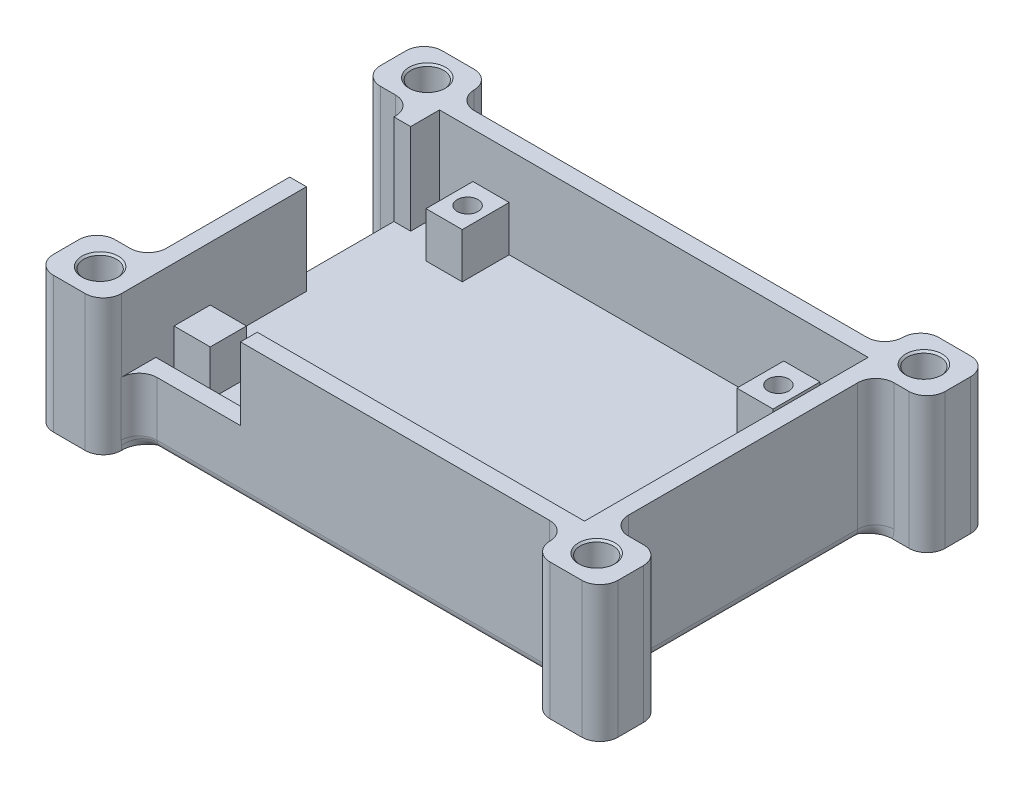
SolidWorks part; units mm, degrees
ref_plane "Płaszczyzna przednia" through (0, 0, 0) normal (0, 0, 1) x (1, 0, 0)
ref_plane "Płaszczyzna górna" through (0, 0, 0) normal (0, 1, 0) x (1, 0, 0)
ref_plane "Płaszczyzna prawa" through (0, 0, 0) normal (1, 0, 0) x (0, 0, -1)
sketch "Szkic1" plane through (0, 0, 0) normal (0, 1, 0) x (1, 0, 0)
  line L1 (-23.65, -15.65) -> (23.65, -15.65)
  line L2 (-23.65, -15.65) -> (-23.65, 15.65)
  line L3 (-23.65, 15.65) -> (23.65, 15.65)
  line L4 (23.65, -15.65) -> (23.65, 15.65)
  line L5 (-23.65, -15.65) -> (23.65, 15.65) construction
  line L6 (-23.65, 15.65) -> (23.65, -15.65) construction
  point P0 (0, 0)
  dimension "D1" = 47.3
  dimension "D2" = 31.3
extrude "Dodanie-wyciągnięcie1" add sketch "Szkic1" along normal blind 10
shell "Skorupa1" thickness 5 removed face at (0, 10, 0) outward yes
sketch "Szkic4" plane through (0, 0, 0) normal (0, 1, 0) x (1, 0, 0)
  line L0 (23.65, -15.65) -> (23.65, 15.65) construction
  line L1 (23.65, 15.65) -> (-23.65, 15.65) construction
  line L2 (-23.65, 15.65) -> (-23.65, -15.65) construction
  line L3 (23.65, 15.65) -> (-23.65, 15.65) construction
  line L4 (-23.65, -15.65) -> (23.65, -15.65) construction
  line L6 (23.65, -15.65) -> (23.65, 15.65) construction
  line L7 (-19.96, 10.47) -> (-15.96, 10.47)
  line L8 (-19.96, 10.47) -> (-19.96, 15.65)
  line L9 (-19.96, 15.65) -> (-15.96, 15.65)
  line L10 (-15.96, 10.47) -> (-15.96, 15.65)
  line L11 (-19.96, 10.47) -> (-15.96, 15.65) construction
  line L12 (-19.96, 15.65) -> (-15.96, 10.47) construction
  line L13 (14.34, 10.47) -> (18.34, 10.47)
  line L14 (14.34, 10.47) -> (14.34, 15.65)
  line L15 (14.34, 15.65) -> (18.34, 15.65)
  line L16 (18.34, 10.47) -> (18.34, 15.65)
  line L17 (14.34, 10.47) -> (18.34, 15.65) construction
  line L18 (14.34, 15.65) -> (18.34, 10.47) construction
  circle A0 centre (-17.96, 13.06) radius 1.15
  circle A1 centre (16.34, 13.06) radius 1.15
  circle A2 centre (5.63, -12.865) radius 1.15
  point P16 (-11.417, 13.06)
  dimension "D1" = 2.3
  dimension "D2" = 7.31
  dimension "D3" = 2.59
  dimension "D4" = 5.69
  dimension "D5" = 2.59
  dimension "D6" = 2.785
  dimension "D7" = 18.02
  dimension "D8" = 4
  dimension "D9" = 4
extrude "Dodanie-wyciągnięcie2" add sketch "Szkic4" along normal blind 5
sketch "Szkic5" plane through (0, 0, 20.65) normal (0, 0, 1) x (1, 0, 0)
  line L0 (-28.65, 10) -> (-28.65, -5) construction
  line L1 (-23.56, 10) -> (-12.46, 10)
  line L2 (-23.56, 10) -> (-23.56, 2)
  line L3 (-23.56, 2) -> (-12.46, 2)
  line L4 (-12.46, 10) -> (-12.46, 2)
  line L7 (-28.65, 10) -> (28.65, 10) construction
  point P0 (-19.96, 7.5)
  dimension "D1" = 7.5
  dimension "D2" = 8.69
  dimension "D3" = 8
  dimension "D4" = 0
extrude "Wytnij-wyciągnięcie2" cut sketch "Szkic5" against normal blind 7
sketch "Szkic7" plane through (0, -5, 0) normal (0, -1, 0) x (1, 0, 0)
  line L0 (-28.65, 20.65) -> (28.65, 20.65) construction
  line L1 (-10.65, 0.65) -> (-4.65, 0.65)
  line L2 (-10.65, 0.65) -> (-10.65, 6.65)
  line L3 (-10.65, 6.65) -> (-4.65, 6.65)
  line L4 (-4.65, 0.65) -> (-4.65, 6.65)
  line L5 (-10.65, 0.65) -> (-4.65, 6.65) construction
  line L6 (-10.65, 6.65) -> (-4.65, 0.65) construction
  line L7 (-28.65, -20.65) -> (-28.65, 20.65) construction
  point P0 (-7.65, 3.65)
  dimension "D1" = 14
  dimension "D2" = 18
  dimension "D3" = 6
  dimension "D4" = 6
extrude "Wytnij-wyciągnięcie4" [suppressed] cut sketch "Szkic7" against normal blind 7
sketch "Szkic8" plane through (0, -5, 0) normal (0, -1, 0) x (1, 0, 0)
  line L1 (-25.5, -17.5) -> (25.5, -17.5)
  line L2 (-25.5, -17.5) -> (-25.5, 17.5)
  line L3 (-25.5, 17.5) -> (25.5, 17.5)
  line L4 (25.5, -17.5) -> (25.5, 17.5)
  line L5 (-25.5, -17.5) -> (25.5, 17.5) construction
  line L6 (-25.5, 17.5) -> (25.5, -17.5) construction
  line L7 (-28.65, -20.65) -> (28.65, -20.65)
  line L8 (-28.65, -20.65) -> (-28.65, 20.65)
  line L9 (-28.65, 20.65) -> (28.65, 20.65)
  line L10 (28.65, -20.65) -> (28.65, 20.65)
  line L11 (-28.65, -20.65) -> (28.65, 20.65) construction
  line L12 (-28.65, 20.65) -> (28.65, -20.65) construction
  point P0 (0, 0)
  point P6 (0, 0)
  dimension "D1" = 51
  dimension "D2" = 35
extrude "Wytnij-wyciągnięcie5" cut sketch "Szkic8" against normal blind 17
fillet "Zaokrąglenie1" [suppressed] radius 2
sketch "Szkic9" plane through (0, 0, 0) normal (0, 1, 0) x (1, 0, 0)
  line L0 (23.65, -15.65) -> (23.65, 15.65) construction
  line L1 (18.65, -10.65) -> (22.65, -10.65)
  line L2 (18.65, -10.65) -> (18.65, -14.65)
  line L3 (18.65, -14.65) -> (22.65, -14.65)
  line L4 (22.65, -10.65) -> (22.65, -14.65)
  line L5 (18.65, -10.65) -> (22.65, -14.65) construction
  line L6 (18.65, -14.65) -> (22.65, -10.65) construction
  line L7 (-12.46, -15.65) -> (23.65, -15.65) construction
  line L8 (0, 0) -> (0, -15.65) construction
  line L9 (-23.65, -15.65) -> (23.65, -15.65) construction
  line L10 (-22.65, -10.65) -> (-22.65, -14.65)
  line L11 (-18.65, -10.65) -> (-18.65, -14.65)
  line L12 (-18.65, -10.65) -> (-22.65, -10.65)
  line L13 (-18.65, -14.65) -> (-22.65, -14.65)
  point P0 (20.65, -12.65)
  dimension "D1" = 4
  dimension "D2" = 4
  dimension "D3" = 5
  dimension "D4" = 5
extrude "Dodanie-wyciągnięcie3" add sketch "Szkic9" along normal blind 5 contours L13 L11 L12 L10 | L1 L4 L3 L2 region at (-20.65, 0, 12.65)
sketch "Szkic6" plane through (-25.5, 0, 0) normal (-1, 0, 0) x (0, 0, 1)
  line L13 (-0.9672, 0) -> (-12.4672, 0)
  line L14 (-0.9672, 0) -> (-0.9672, 10)
  line L15 (-0.9672, 10) -> (-12.4672, 10)
  line L16 (-12.4672, 0) -> (-12.4672, 10)
  line L17 (-0.9672, 0) -> (-12.4672, 10) construction
  line L18 (-0.9672, 10) -> (-12.4672, 0) construction
  point P0 (-8, 3)
  point P5 (-8, 3)
  point P10 (-6.7172, 5)
  dimension "D1" = 11.5
extrude "Wytnij-wyciągnięcie3" cut sketch "Szkic6" against normal blind 2
extrude "Wytnij-wyciągnięcie6" cut sketch "Szkic4<2>" against normal blind 10 contours A1 | A2 | A0 region at (16.34, 0, -13.06) region at (5.63, 0, 12.865)
sketch "Szkic4<2>" plane through (0, 0, 0) normal (0, 1, 0) x (1, 0, 0) same geometry as "Szkic4"
sketch "Szkic10" plane through (0, -5, 0) normal (0, -1, 0) x (1, 0, 0)
  line L0 (5.63, 17.5) -> (5.63, 9.0163) construction
  line L2 (7.993, 12.7243) -> (7.9225, 12.865)
  line L3 (5.7518, 14.9114) -> (5.63, 14.9186)
  line L6 (5.5082, 10.8186) -> (5.63, 10.8114)
  line L19 (25.5, 17.5) -> (-25.5, 17.5) construction
  line L20 (5.63, 12.865) -> (9.7087, 12.865) construction
  line L21 (16.34, -13.06) -> (16.34, -10.331) construction
  line L22 (6.6896, 10.7483) -> (7.3413, 11.7363) [skipped]
  line L23 (3.267, 13.0057) -> (3.7969, 11.9473) [skipped]
  line L24 (4.5704, 14.9817) -> (3.9187, 13.9937) [skipped]
  line L25 (7.9971, 12.865) -> (6.8136, 14.915)
  line L26 (6.8136, 14.915) -> (4.4464, 14.915)
  line L27 (4.4464, 14.915) -> (3.2629, 12.865)
  line L28 (3.2629, 12.865) -> (4.4464, 10.815)
  line L29 (4.4464, 10.815) -> (6.8136, 10.815)
  line L30 (6.8136, 10.815) -> (7.9971, 12.865)
  line L31 (16.34, -13.06) -> (19.1063, -13.06) construction
  line L32 (-17.96, -13.06) -> (-17.96, -9.9123) construction
  line L33 (18.7071, -13.06) -> (17.5236, -11.01)
  line L34 (17.5236, -11.01) -> (15.1564, -11.01)
  line L35 (15.1564, -11.01) -> (13.9729, -13.06)
  line L36 (13.9729, -13.06) -> (15.1564, -15.11)
  line L37 (15.1564, -15.11) -> (17.5236, -15.11)
  line L38 (17.5236, -15.11) -> (18.7071, -13.06)
  line L39 (-17.96, -13.06) -> (-14.4053, -13.06) construction
  line L41 (-15.5929, -13.06) -> (-16.7764, -11.01)
  line L42 (-16.7764, -11.01) -> (-19.1436, -11.01)
  line L43 (-19.1436, -11.01) -> (-20.3271, -13.06)
  line L44 (-20.3271, -13.06) -> (-19.1436, -15.11)
  line L45 (-19.1436, -15.11) -> (-16.7764, -15.11)
  line L46 (-16.7764, -15.11) -> (-15.5929, -13.06)
  circle A2 centre (5.63, 12.865) radius 2.3671
  circle A3 centre (16.34, -13.06) radius 2.05 construction
  circle A4 centre (16.34, -13.06) radius 2.3671
  circle A5 centre (-17.96, -13.06) radius 2.05 construction
  circle A6 centre (-17.96, -13.06) radius 2.3671
  circle M11 centre (16.34, -13.06) radius 1.15
  circle M13 centre (-17.96, -13.06) radius 1.15
  dimension "D3" = 4.1
extrude "Wytnij-wyciągnięcie7" cut sketch "Szkic10" against normal blind 4 contours M13 | M11 | L25 L26 L27 L28 L29 L30 region at (18.0611, -5, -14.0537) region at (-16.2389, -5, -14.0537)
fillet "Zaokrąglenie4" radius 1 4 edges at (0, -5, 17.5) (-25.5, -5, 0) (25.5, -5, 0) (0, -5, -17.5)
fillet "Zaokrąglenie6" [suppressed] radius 1.5
sketch "Szkic11" plane through (0, 10, 0) normal (0, 1, 0) x (1, 0, 0)
  line L1 (-23.65, -21.4503) -> (-31.15, -21.4503)
  line L2 (-23.65, -21.4503) -> (-23.65, -14.6503)
  line L3 (-23.65, -14.6503) -> (-31.15, -14.6503)
  line L4 (-31.15, -21.4503) -> (-31.15, -14.6503)
  line L5 (-23.65, -21.4503) -> (-31.15, -14.6503) construction
  line L6 (-23.65, -14.6503) -> (-31.15, -21.4503) construction
  line L7 (-28.65, 0) -> (28.65, 0) construction
  line L10 (0, 20.65) -> (0, -20.65) construction
  line L13 (-23.65, 14.6503) -> (-31.15, 14.6503)
  line L14 (-31.15, 21.4503) -> (-31.15, 14.6503)
  line L15 (-23.65, 21.4503) -> (-31.15, 21.4503)
  line L16 (-23.65, 21.4503) -> (-23.65, 14.6503)
  line L17 (23.65, -14.6503) -> (31.15, -14.6503)
  line L18 (31.15, -21.4503) -> (31.15, -14.6503)
  line L19 (23.65, -21.4503) -> (31.15, -21.4503)
  line L20 (23.65, -21.4503) -> (23.65, -14.6503)
  line L21 (23.65, 21.4503) -> (23.65, 14.6503)
  line L22 (23.65, 21.4503) -> (31.15, 21.4503)
  line L23 (31.15, 21.4503) -> (31.15, 14.6503)
  line L24 (23.65, 14.6503) -> (31.15, 14.6503)
  line L25 (-23.65, 0.9672) -> (-23.65, -15.65) construction
  circle A0 centre (-27.4, -18.0503) radius 1.81
  circle A1 centre (-27.4, 18.0503) radius 1.81
  circle A2 centre (27.4, 18.0503) radius 1.81
  circle A3 centre (27.4, -18.0503) radius 1.81
  dimension "D2" = 3.62
  dimension "D1" = 7.5
  dimension "D3" = 6.8
sketch "Szkic12" plane through (0, 10, 0) normal (0, 1, 0) x (1, 0, 0)
  line L0 (-23.65, -21.4503) -> (-31.15, -14.6503) construction
  line L1 (-28.65, 0) -> (28.65, 0) construction
  line L2 (0, 20.65) -> (0, -20.65) construction
  circle A0 centre (-27.4, -18.0503) radius 1.225
  circle A1 centre (-27.4, 18.0503) radius 1.225
  circle A2 centre (27.4, -18.0503) radius 1.225
  circle A3 centre (27.4, 18.0503) radius 1.225
  point P4 (-27.4, -18.0503)
  dimension "D1" = 2.45
extrude "Dodanie-wyciągnięcie4" add sketch "Szkic11" against normal up to surface (15 mm away) up to face at (0, -5, 0)
sketch "Szkic13" plane through (-23.56, 0, 0) normal (1, 0, 0) x (0, 0, -1)
  line L1 (-15.65, 10) -> (-17.5, 10)
  line L2 (-15.65, 10) -> (-15.65, 2)
  line L3 (-15.65, 2) -> (-17.5, 2)
  line L4 (-17.5, 10) -> (-17.5, 2)
extrude "Wytnij-wyciągnięcie9" cut sketch "Szkic13" against normal up to surface (0.09 mm away) up to face at (-23.65, 1.1586, 18.9216)
fillet "Zaokrąglenie7" radius 2 12 edges at (23.65, 2.5, -21.4503) (31.15, 2.5, -21.4503) (31.15, 2.5, -14.6503) (31.15, 2.5, 14.6503) (31.15, 2.5, 21.4503) (23.65, 2.5, 21.4503) (-23.65, 2.5, 21.4503) (-31.15, 2.5, 21.4503) (-31.15, 2.5, 14.6503) (-23.65, 2.5, -21.4503) (-31.15, 2.5, -21.4503) (-31.15, 2.5, -14.6503)
fillet "Zaokrąglenie8" radius 2 15 edges at (23.65, -4.7071, -17.2071) (25.2071, -4.7071, -14.6503) (25.2071, -4.7071, 14.6503) (23.65, -4.7071, 17.2071) (-25.2071, -4.7071, 14.6503) (-25.2071, -4.7071, -14.6503) (-23.65, -4.7071, -17.2071) (23.65, 3, -17.5) (25.5, 3, -14.6503) (25.5, 3, 14.6503) (23.65, 3, 17.5) (-23.65, -1, 17.5) (-25.5, 3, 14.6503) (-25.5, 3, -14.6503) (-23.65, 3, -17.5)
sketch "Szkic16" plane through (0, 5, 0) normal (0, 1, 0) x (1, 0, 0)
  circle A0 centre (5.63, -12.865) radius 1.15
extrude "Wytnij-wyciągnięcie11" cut sketch "Szkic16" against normal blind 10
sketch "Szkic18" plane through (0, 5, 0) normal (0, 1, 0) x (1, 0, 0)
  circle A0 centre (16.34, 13.06) radius 1.15 construction
  point P0 (17.49, 13.06)
sketch "Szkic19" plane through (0, -5, 0) normal (0, -1, 0) x (1, 0, 0)
  line L0 (0, 16.5) -> (0, -16.5) construction
  line L1 (21.65, 16.5) -> (-21.65, 16.5) construction
  line L2 (-21.65, -16.5) -> (21.65, -16.5) construction
  line L3 (-24.5, 0) -> (24.5, 0) construction
  line L4 (-24.5, 12.6503) -> (-24.5, -12.6503) construction
  line L5 (24.5, -12.6503) -> (24.5, 12.6503) construction
  circle A0 centre (-27.4, 18.0503) radius 1.4
  circle A1 centre (-27.4, 18.0503) radius 1.81
  circle A2 centre (27.4, 18.0503) radius 1.4
  circle A3 centre (27.4, 18.0503) radius 1.81
  circle A4 centre (27.4, -18.0503) radius 1.4
  circle A5 centre (27.4, -18.0503) radius 1.81
  circle A6 centre (-27.4, -18.0503) radius 1.4
  circle A7 centre (-27.4, -18.0503) radius 1.81
  dimension "D1" = 2.8
extrude "Dodanie-wyciągnięcie5" add sketch "Szkic19" against normal blind 11.8
chamfer "Sfazowanie1" distance 0.2 angle 45 4 edges at (-27.4, 10, -19.8603) (-27.4, 10, 19.8603) (27.4, 10, -16.2403) (27.4, 10, 16.2403)
